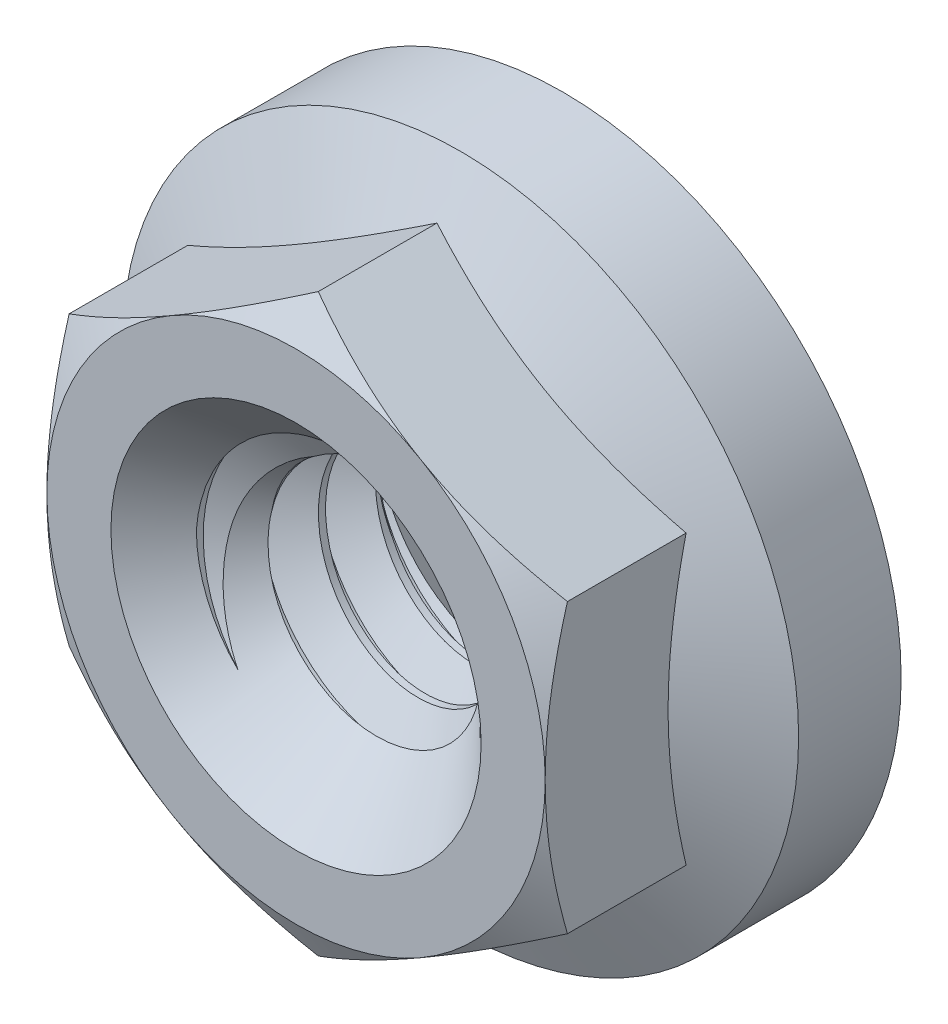
SolidWorks part; units mm, degrees
ref_plane "Front Plane" through (0, 0, 0) normal (0, 0, 1) x (1, 0, 0)
ref_plane "Top Plane" through (0, 0, 0) normal (0, 1, 0) x (1, 0, 0)
ref_plane "Right Plane" through (0, 0, 0) normal (1, 0, 0) x (0, 0, -1)
sketch "Sketch1" plane through (0, 0, 0) normal (0, 0, 1) x (1, 0, 0)
  line L0 (-2.7496, -1.5875) -> (0, 0) construction
  line L1 (0, 6.4158) -> (-5.5563, 3.2079)
  line L2 (-5.5563, 3.2079) -> (-5.5563, -3.2079)
  line L3 (-5.5563, -3.2079) -> (0, -6.4158)
  line L4 (0, -6.4158) -> (5.5562, -3.2079)
  line L5 (5.5562, -3.2079) -> (5.5562, 3.2079)
  line L6 (5.5562, 3.2079) -> (0, 6.4158)
  circle A0 centre (0, 0) radius 5.5563 construction
  circle A1 centre (0, 0) radius 7.5406
  circle A2 centre (0, 0) radius 3.175
  point P11 (-2.7496, -1.5875)
  dimension "Flange Diameter" = 15.0812
  dimension "Thread Size" = 6.35
  dimension "Width" = 11.1125
sketch "Sketch2" plane through (0, 0, 0) normal (1, 0, 0) x (0, 0, -1)
  line L0 (-2.9766, 0) -> (2.9766, 0) construction
  line L3 (0, 7.5406) -> (0, -7.5406) construction
  line L6 (-4.1672, 3.3125) -> (-3.5322, 2.2126) construction
  line L7 (-3.5322, 2.2126) -> (-2.8972, 3.3125) construction
  line L8 (-2.8972, 3.3125) -> (-4.1672, 3.3125) construction
  line L9 (-4.0878, 3.175) -> (-2.9766, 3.175) construction
  line L10 (-3.5322, 3.3125) -> (-3.5322, 3.175) construction
  line L11 (-3.5322, 3.175) -> (-3.5322, 2.3501) construction
  line L12 (-3.5322, 2.3501) -> (-3.5322, 2.2126) construction
  line L13 (-3.6116, 2.3501) -> (-3.4528, 2.3501)
  line L14 (-4.1275, 3.2437) -> (-2.9369, 3.2437)
  line L15 (-3.4528, 2.3501) -> (-2.9369, 3.2437)
  line L16 (-3.6116, 2.3501) -> (-4.1275, 3.2437)
  point P3 (2.9766, -7.5406)
  point P4 (0, 3.175)
  point P5 (-2.9766, -7.5406)
  point P10 (0, -7.5406)
  point P13 (0.6906, -7.5406)
  point P25 (-3.5322, 3.2437)
  dimension "Height" = 5.9531
  dimension "Flange Thickness" = 2.286
  dimension "Thread Pitch" = 1.27
  dimension "D2" = 0.1588
sketch "Sketch3" plane through (0, 0, 0) normal (0, 0, 1) x (1, 0, 0)
  circle A0 centre (0, 0) radius 3.175 construction
  circle A1 centre (0, 0) radius 7.5406 construction
  circle A2 centre (0, 0) radius 3.175
  circle A3 centre (0, 0) radius 7.5406
extrude "Boss-Extrude1" add sketch "Sketch3" along normal up to vertex (-0.6906 mm away) from vertex up to point (0, -7.5406, -0.6906) starting at point (0, -7.5406, -2.9766)
sketch "Sketch4" plane through (0, 0, -0.6906) normal (0, 0, 1) x (1, 0, 0)
  line L0 (5.5562, 3.2079) -> (0, 6.4158) construction
  line L1 (5.5562, -3.2079) -> (5.5562, 3.2079) construction
  line L2 (0, -6.4158) -> (5.5562, -3.2079) construction
  line L3 (-5.5563, -3.2079) -> (0, -6.4158) construction
  line L4 (-5.5563, 3.2079) -> (-5.5563, -3.2079) construction
  line L5 (0, 6.4158) -> (-5.5563, 3.2079) construction
  line L6 (5.5562, 3.2079) -> (0, 6.4158)
  line L7 (5.5562, -3.2079) -> (5.5562, 3.2079)
  line L8 (0, -6.4158) -> (5.5562, -3.2079)
  line L9 (-5.5563, -3.2079) -> (0, -6.4158)
  line L10 (-5.5563, 3.2079) -> (-5.5563, -3.2079)
  line L11 (0, 6.4158) -> (-5.5563, 3.2079)
  circle A0 centre (0, 0) radius 3.175 construction
  circle A1 centre (0, 0) radius 3.175
extrude "Boss-Extrude2" add sketch "Sketch4" along normal up to vertex (3.6671 mm away) up to point (0, -7.5406, 2.9766)
sketch "Sketch5" plane through (0, 0, 0) normal (1, 0, 0) x (0, 0, -1)
  line L0 (-2.4803, 6.4158) -> (-2.9766, 5.5563)
  line L1 (-2.9766, 6.4158) -> (0.6906, 6.4158) construction
  line L2 (-2.9766, 3.2079) -> (-2.9766, 6.4158) construction
  line L3 (-2.9766, 5.5563) -> (-2.9766, 6.4158)
  line L4 (-2.9766, 6.4158) -> (-2.4803, 6.4158)
  line L5 (-2.9766, 5.5563) -> (0, 5.5563) construction
  dimension "D1" = 30
revolve "Cut-Revolve1" cut sketch "Sketch5" angle 360 about L0
chamfer "Chamfer1" distance 0.9525 angle 45 2 edges at (3.175, 0, -2.9766) (3.175, 0, 2.9766)
sketch "Sketch11" plane through (0, 0, 0) normal (1, 0, 0) x (0, 0, -1)
  line L0 (0.6906, 7.5406) -> (-1.3452, 3.175)
  line L1 (-1.3452, 3.175) -> (-1.3452, 7.5406) construction
  line L2 (-1.3452, 7.5406) -> (0.6906, 7.5406) construction
  line L3 (-1.3452, 3.175) -> (0.6906, 3.175)
  line L4 (0.6906, 3.175) -> (0.6906, 7.5406)
  dimension "D1" = 25
revolve "Revolve1" add sketch "Sketch11" angle 360 about L0
sketch "Sketch6" plane through (0, 0, 2.9766) normal (0, 0, 1) x (1, 0, 0)
  circle A0 centre (0, 0) radius 3.175 construction
  circle A1 centre (0, 0) radius 3.175
curve "Helix/Spiral1" pitch 1.27 height 7.2231 radius 3.175 centre (0, 0, 2.9766) axis (0, 0, -1) start towards (0, 1, 0)
sketch "Sketch7" plane through (0, 0, 0) normal (1, 0, 0) x (0, 0, -1)
  line L0 (-3.6116, 2.3501) -> (-3.4528, 2.3501) construction
  line L1 (-3.4528, 2.3501) -> (-2.9369, 3.2437) construction
  line L2 (-4.1275, 3.2437) -> (-2.9369, 3.2437) construction
  line L3 (-3.6116, 2.3501) -> (-4.1275, 3.2437) construction
  line L4 (-3.6116, 2.3501) -> (-3.4528, 2.3501)
  line L5 (-3.4528, 2.3501) -> (-2.9369, 3.2437)
  line L6 (-4.1275, 3.2437) -> (-2.9369, 3.2437)
  line L7 (-3.6116, 2.3501) -> (-4.1275, 3.2437)
sweep "Sweep1" add profiles "Sketch7" path "Helix/Spiral1"
sketch "Sketch9" plane through (0, 0, 2.9766) normal (0, 0, 1) x (1, 0, 0)
  circle A0 centre (0, 0) radius 4.1275 construction
  circle A1 centre (0, 0) radius 4.1275
extrude "Cut-Extrude1" cut sketch "Sketch9" against normal through all draft 45 and the other way through all
sketch "Sketch10" plane through (0, 0, -2.9766) normal (0, 0, -1) x (-1, 0, 0)
  circle A0 centre (0, 0) radius 4.1275 construction
  circle A1 centre (0, 0) radius 4.1275
extrude "Cut-Extrude2" cut sketch "Sketch10" against normal through all draft 45 and the other way through all
equation "\"D2@Sketch2\" = \"Thread Pitch@Sketch2\" / 8"
equation "\"D1@Chamfer1\" = \"Thread Pitch@Sketch2\" * 0.75"
equation "\"D3@Helix/Spiral1\"=\"Height@Sketch2\"+\"Thread Pitch@Sketch2\""
equation "\"D4@Helix/Spiral1\" = \"Thread Pitch@Sketch2\""
